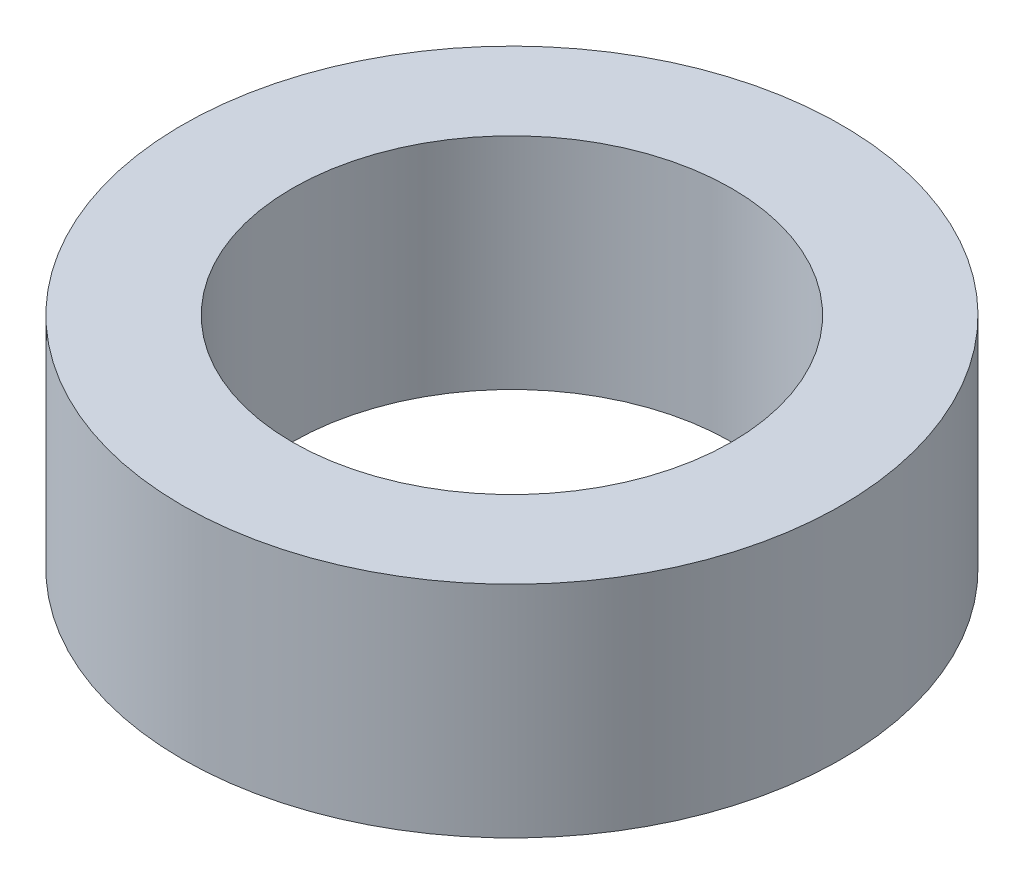
SolidWorks part; units mm, degrees
material "ABS"
ref_plane "Ebene vorne" through (0, 0, 0) normal (0, 0, 1) x (1, 0, 0)
ref_plane "Ebene oben" through (0, 0, 0) normal (0, 1, 0) x (1, 0, 0)
ref_plane "Ebene rechts" through (0, 0, 0) normal (1, 0, 0) x (0, 0, -1)
sketch "Skizze1" plane through (0, 0, 0) normal (0, 1, 0) x (1, 0, 0)
  circle A0 centre (0, 0) radius 7.5
  circle A1 centre (0, 0) radius 5
  dimension "D1" = 15
  dimension "D2" = 10
extrude "Aufsatz-Linear austragen1" add sketch "Skizze1" along normal blind 5
